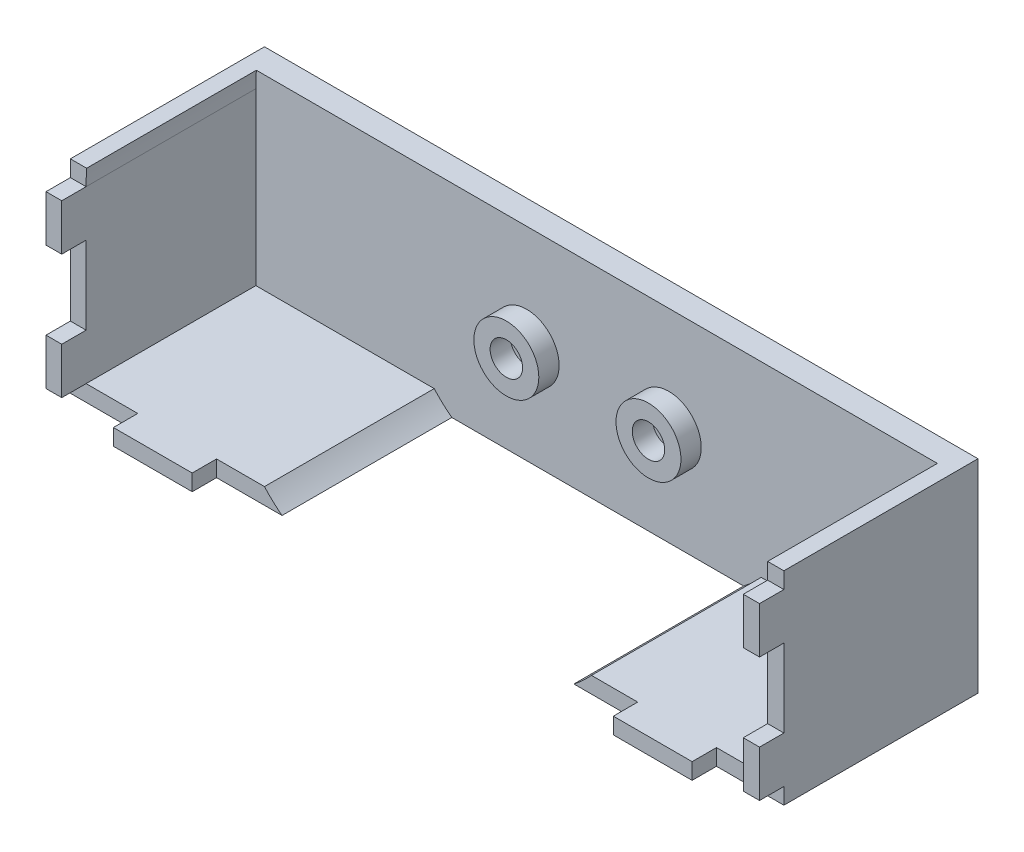
SolidWorks part; units mm, degrees
ref_plane "Plano frontal" through (0, 0, 0) normal (0, 0, 1) x (1, 0, 0)
ref_plane "Plano superior" through (0, 0, 0) normal (0, 1, 0) x (1, 0, 0)
ref_plane "Plano direito" through (0, 0, 0) normal (1, 0, 0) x (0, 0, -1)
sketch "Esboço1" plane through (0, 0, 0) normal (0, 0, 1) x (1, 0, 0)
  line L0 (54.3814, -10.6678) -> (-10.9255, -10.6678)
  line L1 (-8.9871, 12.3322) -> (-8.9871, -8.6678)
  line L2 (-10.9255, 12.3322) -> (-8.9871, 12.3322)
  line L3 (-10.9255, -8.6678) -> (76.9288, -8.6678)
  line L4 (76.9288, 14.3322) -> (76.9288, -8.6678)
  line L5 (-10.9255, -10.6678) -> (-8.9255, -10.6678)
  line L6 (76.9288, 14.3322) -> (-10.9255, 14.3322)
  line L7 (76.9288, -8.6678) -> (76.9288, -10.6678)
  line L8 (-8.9255, 14.3322) -> (-10.9255, 14.3322)
  line L9 (-8.9871, 12.3322) -> (-8.9871, -2.9678)
  line L10 (66.0745, 14.3322) -> (54.0745, 14.3322)
  line L11 (-8.9871, 6.6322) -> (-10.9255, 6.6322)
  line L12 (-10.9255, 14.3322) -> (-10.9255, -8.6678)
  line L13 (-10.9255, 6.6322) -> (-10.9255, -8.6678)
  line L14 (-10.9255, 14.3322) -> (-8.9255, 14.3322)
  line L15 (-8.9871, -2.9678) -> (-8.9871, -6.6678)
  line L16 (-10.9255, -2.9678) -> (-8.9871, -2.9678)
  line L17 (76.9288, -10.6678) -> (54.3814, -10.6678)
  line L18 (-2.6255, -10.6678) -> (-2.6255, -8.6678)
  line L19 (7.0745, -8.6678) -> (7.0745, -10.6678)
  line L20 (58.9288, -8.6678) -> (58.9288, -10.6678)
  line L21 (68.6288, -8.6678) -> (68.6288, -10.6678)
  line L22 (74.9288, 14.3322) -> (74.9288, -8.6678)
  line L23 (74.9288, 12.3322) -> (76.9288, 12.3322)
  line L24 (28.5745, 14.3322) -> (16.5745, 14.3322)
  line L25 (-10.9255, -8.6678) -> (-8.9871, -8.6678)
  line L26 (74.9288, 6.6322) -> (76.9288, 6.6322)
  line L27 (54.3814, -10.6678) -> (42.3814, -10.6678)
  line L28 (74.9288, -2.9678) -> (76.9288, -2.9678)
  line L29 (15.7279, -10.6678) -> (27.7279, -10.6678)
  line L32 (-8.9871, 12.3322) -> (-8.9871, 6.6322)
  line L34 (-10.9255, -8.6678) -> (-10.9255, -10.6678)
  circle A0 centre (24.3545, 1.4822) radius 2
  circle A1 centre (41.8545, 1.4822) radius 2
  circle A2 centre (24.3545, 1.4822) radius 15.25
  circle A3 centre (24.3545, 1.4822) radius 4
  circle A4 centre (41.8545, 1.4822) radius 4
  circle A5 centre (41.8545, 1.4822) radius 15.25
  arc A6 (-8.9871, 12.3322) -> (-8.9255, 14.3322) centre (23.5312, 12.3322) cw
  circle A7 centre (7.0745, 1.4822) radius 4.5
  point P4 (24.0129, -8.6678)
  point P5 (24.0129, -8.6678)
  dimension "D4" = 4
  dimension "D6" = 8
  dimension "D9" = 25
  dimension "D17" = 9
  dimension "D11" = 30.5
  dimension "D13" = 30.5
  dimension "D25" = 4
  dimension "D26" = 8
  dimension "D3" = 5.7
  dimension "D5" = 8.3
  dimension "D7" = 17.5
  dimension "D8" = 17.5
  dimension "D10" = 17.28
  dimension "D12" = 2
  dimension "D14" = 2
  dimension "D15" = 5.7
  dimension "D16" = 9.7
  dimension "D18" = 25
  dimension "D19" = 8.3
  dimension "D20" = 9.7
  dimension "D21" = 12
  dimension "D22" = 2
  dimension "D23" = 10.15
  dimension "D24" = 10.15
extrude "Ressalto-extrusão1" add sketch "Esboço1" along normal blind 3 contours A7 A2 L24 L6 A6 L1 L9 L3 | A2 A7 | A2 A7 | A7 A2 L3 A5 A3 L6 | A5 A3 A0 | A0 | A3 A5 | A2 A5 A3 L3 A4 | A2 A4 | A2 A4 A1 | A1 | L6 A5 A2 A4 L3 | A5 L6 A2 | L2 A6 L6 L12 | L2 L12 L11 L1 | L12 L16 L9 L11 | L16 L13 L3 L1 | L3 L34 L0 L18 | L19 L3 L18 L0 | A2 L3 L19 L0 | A5 L3 A2 L0 | L3 A5 L0 A2 | L27 A5 L3 A2 L0 | A5 L0 L17 L20 L3 | L21 L3 L20 L17 | L3 L21 L17 L7 | L28 L22 L3 L4 | A5 L3 L22 L6 | L22 L28 L4 L26 | L22 L26 L4 L23 | L22 L23 L4 L6 region at (22.7354, -9.6678, 0) region at (10.558, -9.7198, 0) region at (33.1045, -9.4458, 0) region at (2.2245, -9.6678, 0) region at (19.3615, 3.043, 0) region at (0.3178, 3.2824, 0) region at (43.4736, -9.6678, 0) region at (33.1045, 1.8347, 0) region at (-6.7755, -9.6678, 0) region at (6.2784, 1.4822, 0) region at (10.2077, 1.4822, 0) region at (55.5472, -9.7214, 0) region at (47.1756, 2.987, 0) region at (27.3791, 1.4822, 0) region at (20.4579, 1.4822, 0) region at (65.093, 3.0861, 0) region at (38.8298, 1.4822, 0) region at (39.6291, -0.0719, 0) region at (-9.9563, -5.8178, 0) region at (63.7788, -9.6678, 0) region at (33.1045, 14.2131, 0) region at (-9.946, 13.3374, 0) region at (72.7788, -9.6678, 0) region at (-9.9563, 1.8322, 0) region at (-9.9563, 9.4822, 0) region at (75.9288, -5.8178, 0) region at (75.9288, 1.8322, 0) region at (75.9288, 9.4822, 0) region at (75.9288, 13.3322, 0) region at (24.3545, 1.4822, 0) region at (41.8545, 1.4822, 0)
extrude "Ressalto-extrusão2" add sketch "Esboço1<11>" along normal blind 5.5 contours A5 A3 A0 | A3 A5 | A2 A4 A1 | A2 A4 region at (27.3791, 1.4822, 0) region at (20.4579, 1.4822, 0) region at (38.8298, 1.4822, 0) region at (39.6291, -0.0719, 0)
sketch "Esboço1<11>" plane through (0, 0, 0) normal (0, 0, 1) x (1, 0, 0) same geometry as "Esboço1"
extrude "Ressalto-extrusão3" add sketch "Esboço1<12>" along normal blind 23.9 contours L2 A6 L6 L12 | L2 L12 L11 L1 | L12 L16 L9 L11 | L16 L13 L3 L1 | L3 L34 L0 L18 | L19 L3 L18 L0 | A2 L3 L19 L0 | A5 L0 L17 L20 L3 | L21 L3 L20 L17 | L3 L21 L17 L7 | L28 L22 L3 L4 | L22 L28 L4 L26 | L22 L26 L4 L23 | L22 L23 L4 L6 region at (10.558, -9.7198, 0) region at (2.2245, -9.6678, 0) region at (-6.7755, -9.6678, 0) region at (55.5472, -9.7214, 0) region at (-9.9563, -5.8178, 0) region at (63.7788, -9.6678, 0) region at (-9.946, 13.3374, 0) region at (72.7788, -9.6678, 0) region at (-9.9563, 1.8322, 0) region at (-9.9563, 9.4822, 0) region at (75.9288, -5.8178, 0) region at (75.9288, 1.8322, 0) region at (75.9288, 9.4822, 0) region at (75.9288, 13.3322, 0)
sketch "Esboço1<12>" plane through (0, 0, 0) normal (0, 0, 1) x (1, 0, 0) same geometry as "Esboço1"
extrude "Ressalto-extrusão4" add sketch "Esboço1<13>" along normal blind 26.9 contours L2 L12 L11 L1 | L16 L13 L3 L1 | L19 L3 L18 L0 | L21 L3 L20 L17 | L22 L26 L4 L23 | L28 L22 L3 L4 region at (2.2245, -9.6678, 0) region at (-9.9563, -5.8178, 0) region at (63.7788, -9.6678, 0) region at (-9.9563, 9.4822, 0) region at (75.9288, -5.8178, 0) region at (75.9288, 9.4822, 0)
sketch "Esboço1<13>" plane through (0, 0, 0) normal (0, 0, 1) x (1, 0, 0) same geometry as "Esboço1"
